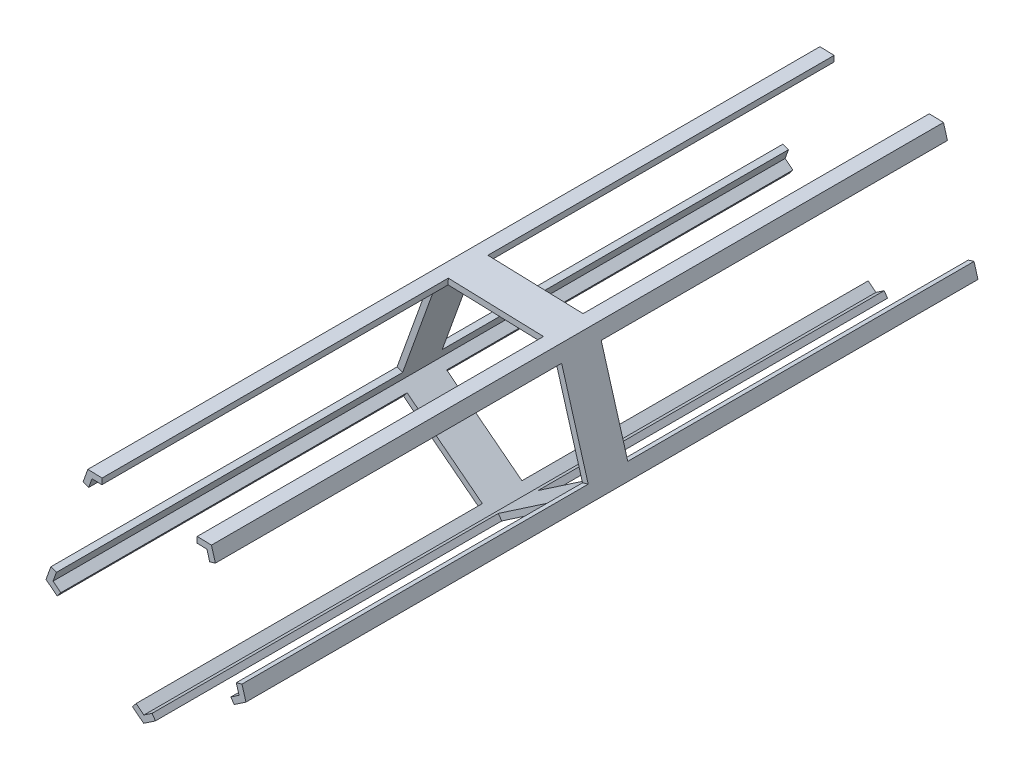
SolidWorks part; units mm, degrees
ref_plane "Front Plane" through (0, 0, 0) normal (0, 0, 1) x (1, 0, 0)
ref_plane "Top Plane" through (0, 0, 0) normal (0, 1, 0) x (1, 0, 0)
ref_plane "Right Plane" through (0, 0, 0) normal (1, 0, 0) x (0, 0, -1)
sketch "Sketch3" plane through (0, 0, 0) normal (0, 0, 1) x (1, 0, 0)
  line L0 (0, 0) -> (16.2851, 21.0012) construction
  line L1 (15.1489, 19.536) -> (-13.8986, 20.4445)
  line L2 (-13.8986, 20.4445) -> (-23.7387, -6.9006)
  line L3 (-23.7387, -6.9006) -> (-0.7728, -24.7093)
  line L4 (-0.7728, -24.7093) -> (23.2611, -8.3705)
  line L10 (-0.8307, -26.5625) -> (25.0057, -8.9983)
  line L11 (25.0057, -8.9983) -> (16.2851, 21.0012)
  line L12 (16.2851, 21.0012) -> (-14.941, 21.9778)
  line L13 (-14.941, 21.9778) -> (-25.5191, -7.4182)
  line L14 (-25.5191, -7.4182) -> (-0.8307, -26.5625)
  line L15 (23.2611, -8.3705) -> (15.1489, 19.536)
  circle A0 centre (0, 0) radius 20 construction
  dimension "D2" = 40
extrude "Boss-Extrude2" add sketch "Sketch3" along normal blind 185
ref_plane "Plane1" through (0, 0, 92.5) normal (0, 0, 1) x (1, 0, 0)
sketch "Sketch4" plane through (0, 0, 0) normal (0, 0, -1) x (-1, 0, 0)
  line L0 (14.745, 18.0921) -> (16.1564, 18.6)
  line L1 (13.8986, 20.4445) -> (23.7387, -6.9006) construction
  line L2 (14.941, 21.9778) -> (25.5191, -7.4182) construction
  line L3 (24.3036, -4.0404) -> (22.8922, -4.5483)
  line L4 (22.8922, -4.5483) -> (14.745, 18.0921)
  line L5 (24.3036, -4.0404) -> (16.1564, 18.6)
  dimension "D1" = 2.5
  dimension "D2" = 2.5
extrude "Cut-Extrude1" cut sketch "Sketch4" against normal offset from surface (87.5 mm away) 5 up to plane "Plane1"
ref_point "Point1"
ref_axis "Axis1" through (0, 0, 185) along (0, 0, 1)
pattern_circular "CirPattern1" count 5 over 360 about axis through (0, 0, 185) along (0, 0, 1) of "Cut-Extrude1"
mirror "Mirror1" about plane through (0, 0, 92.5) normal (0, 0, 1) of "CirPattern1"
